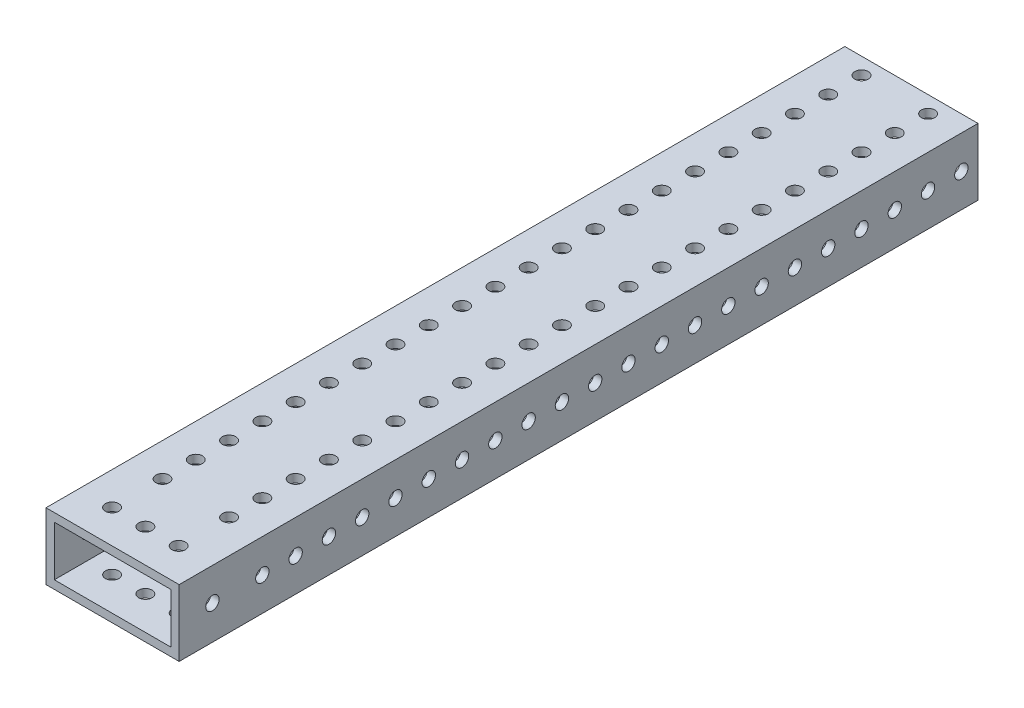
SolidWorks part; units mm, degrees
material "6061-T6 (SS)"
ref_plane "Front Plane" through (0, 0, 0) normal (0, 0, 1) x (1, 0, 0)
ref_plane "Top Plane" through (0, 0, 0) normal (0, 1, 0) x (1, 0, 0)
ref_plane "Right Plane" through (0, 0, 0) normal (1, 0, 0) x (0, 0, -1)
sketch "Sketch1" plane through (0, 0, 0) normal (0, 1, 0) x (1, 0, 0)
  line L1 (0, 0) -> (50.8, 0)
  line L2 (0, 0) -> (0, 304.8)
  line L3 (0, 304.8) -> (50.8, 304.8)
  line L4 (50.8, 0) -> (50.8, 304.8)
  dimension "D1" = 50.8
  dimension "D2" = 304.8
extrude "Boss-Extrude1" add sketch "Sketch1" along normal blind 25.4
sketch "Sketch2" plane through (0, 0, 0) normal (0, 0, 1) x (1, 0, 0)
  line L3 (3.175, 3.175) -> (47.625, 3.175)
  line L4 (3.175, 3.175) -> (3.175, 22.225)
  line L5 (3.175, 22.225) -> (47.625, 22.225)
  line L6 (47.625, 3.175) -> (47.625, 22.225)
  line L7 (0, 25.4) -> (0, 0) construction
  line L8 (50.8, 25.4) -> (50.8, 0) construction
  line L9 (0, 0) -> (50.8, 0) construction
  line L10 (0, 25.4) -> (50.8, 25.4) construction
  point P8 (25.4, 12.7)
  dimension "D1" = 3.175
  dimension "D2" = 3.175
  dimension "D3" = 3.175
  dimension "D4" = 3.175
extrude "Cut-Extrude1" cut sketch "Sketch2" against normal through all
sketch "Sketch4" plane through (0, 25.4, 0) normal (0, 1, 0) x (1, 0, 0)
  line L0 (0, 0) -> (50.8, 0) construction
  line L1 (0, 304.8) -> (0, 0) construction
  line L2 (50.8, 0) -> (50.8, 304.8) construction
  circle A0 centre (12.7, 6.35) radius 2.5527 construction
  circle A1 centre (38.1, 6.35) radius 2.5527 construction
  circle A2 centre (12.7, 19.05) radius 2.5527 construction
  circle A3 centre (38.1, 19.05) radius 2.5527 construction
  circle A4 centre (12.7, 31.75) radius 2.5527
  circle A5 centre (38.1, 31.75) radius 2.5527
  circle A6 centre (12.7, 44.45) radius 2.5527
  circle A7 centre (38.1, 44.45) radius 2.5527
  circle A8 centre (12.7, 57.15) radius 2.5527
  circle A9 centre (38.1, 57.15) radius 2.5527
  circle A10 centre (12.7, 69.85) radius 2.5527
  circle A11 centre (38.1, 69.85) radius 2.5527
  circle A12 centre (12.7, 82.55) radius 2.5527
  circle A13 centre (38.1, 82.55) radius 2.5527
  circle A14 centre (12.7, 95.25) radius 2.5527
  circle A15 centre (38.1, 95.25) radius 2.5527
  circle A16 centre (12.7, 107.95) radius 2.5527
  circle A17 centre (38.1, 107.95) radius 2.5527
  circle A18 centre (12.7, 120.65) radius 2.5527
  circle A19 centre (38.1, 120.65) radius 2.5527
  circle A20 centre (12.7, 133.35) radius 2.5527
  circle A21 centre (38.1, 133.35) radius 2.5527
  circle A22 centre (12.7, 146.05) radius 2.5527
  circle A23 centre (38.1, 146.05) radius 2.5527
  circle A24 centre (12.7, 158.75) radius 2.5527
  circle A25 centre (38.1, 158.75) radius 2.5527
  circle A26 centre (12.7, 171.45) radius 2.5527
  circle A27 centre (38.1, 171.45) radius 2.5527
  circle A28 centre (12.7, 184.15) radius 2.5527
  circle A29 centre (38.1, 184.15) radius 2.5527
  circle A30 centre (12.7, 196.85) radius 2.5527
  circle A31 centre (38.1, 196.85) radius 2.5527
  circle A32 centre (12.7, 209.55) radius 2.5527
  circle A33 centre (38.1, 209.55) radius 2.5527
  circle A34 centre (12.7, 222.25) radius 2.5527
  circle A35 centre (38.1, 222.25) radius 2.5527
  circle A36 centre (12.7, 234.95) radius 2.5527
  circle A37 centre (38.1, 234.95) radius 2.5527
  circle A38 centre (12.7, 247.65) radius 2.5527
  circle A39 centre (38.1, 247.65) radius 2.5527
  circle A40 centre (12.7, 260.35) radius 2.5527
  circle A41 centre (38.1, 260.35) radius 2.5527
  circle A42 centre (12.7, 273.05) radius 2.5527
  circle A43 centre (38.1, 273.05) radius 2.5527
  circle A44 centre (12.7, 285.75) radius 2.5527
  circle A45 centre (38.1, 285.75) radius 2.5527
  circle A46 centre (12.7, 298.45) radius 2.5527
  circle A47 centre (38.1, 298.45) radius 2.5527
  circle A48 centre (12.7, 311.15) radius 2.5527
  circle A49 centre (38.1, 311.15) radius 2.5527
  circle A50 centre (12.7, 323.85) radius 2.5527
  circle A51 centre (38.1, 323.85) radius 2.5527
  circle A52 centre (12.7, 336.55) radius 2.5527
  circle A53 centre (38.1, 336.55) radius 2.5527
  circle A54 centre (12.7, 349.25) radius 2.5527
  circle A55 centre (38.1, 349.25) radius 2.5527
  circle A56 centre (12.7, 361.95) radius 2.5527
  circle A57 centre (38.1, 361.95) radius 2.5527
  circle A58 centre (12.7, 374.65) radius 2.5527
  circle A59 centre (38.1, 374.65) radius 2.5527
  circle A60 centre (12.7, 387.35) radius 2.5527
  circle A61 centre (38.1, 387.35) radius 2.5527
  circle A62 centre (12.7, 400.05) radius 2.5527
  circle A63 centre (38.1, 400.05) radius 2.5527
  circle A64 centre (12.7, 412.75) radius 2.5527
  circle A65 centre (38.1, 412.75) radius 2.5527
  circle A66 centre (12.7, 425.45) radius 2.5527
  circle A67 centre (38.1, 425.45) radius 2.5527
  circle A68 centre (12.7, 438.15) radius 2.5527
  circle A69 centre (38.1, 438.15) radius 2.5527
  circle A70 centre (12.7, 450.85) radius 2.5527
  circle A71 centre (38.1, 450.85) radius 2.5527
  circle A72 centre (12.7, 463.55) radius 2.5527
  circle A73 centre (38.1, 463.55) radius 2.5527
  circle A74 centre (12.7, 476.25) radius 2.5527
  circle A75 centre (38.1, 476.25) radius 2.5527
  circle A76 centre (12.7, 488.95) radius 2.5527
  circle A77 centre (38.1, 488.95) radius 2.5527
  circle A78 centre (12.7, 501.65) radius 2.5527
  circle A79 centre (38.1, 501.65) radius 2.5527
  circle A81 centre (12.5095, 12.7) radius 2.5527
  circle A82 centre (25.2095, 12.7) radius 2.5527
  circle A84 centre (37.9095, 12.7) radius 2.5527
  dimension "D1" = 6.35
  dimension "D2" = 6.35
  dimension "D3" = 5.1054
  dimension "D4" = 5.1054
  dimension "D5" = 12.7
  dimension "D6" = 12.7
  dimension "D8" = 12.7
  dimension "D9" = 5.1054
  dimension "D10" = 12.5095
  dimension "D11" = 12.7
  dimension "D12" = 5.1054
  dimension "D13" = 12.7
  dimension "D14" = 12.7
  dimension "D15" = 12.7
  dimension "D16" = 5.1054
  dimension "D17" = 12.7
  dimension "D7" = 40
sketch "Sketch5" plane through (0, 0, 0) normal (-1, 0, 0) x (0, 0, 1)
  line L0 (-304.8, 0) -> (0, 0) construction
  line L1 (0, 25.4) -> (0, 0) construction
  line L3 (-116.3974, 0) -> (25.4, 0) construction
  line L4 (25.4, 76.2) -> (25.4, 0) construction
  circle A0 centre (-6.35, 12.7) radius 2.5527 construction
  circle A1 centre (-19.05, 12.7) radius 2.5527 construction
  circle A2 centre (-31.75, 12.7) radius 2.5527
  circle A3 centre (-44.45, 12.7) radius 2.5527
  circle A4 centre (-57.15, 12.7) radius 2.5527
  circle A5 centre (-69.85, 12.7) radius 2.5527
  circle A6 centre (-82.55, 12.7) radius 2.5527
  circle A7 centre (-95.25, 12.7) radius 2.5527
  circle A8 centre (-107.95, 12.7) radius 2.5527
  circle A9 centre (-120.65, 12.7) radius 2.5527
  circle A10 centre (-133.35, 12.7) radius 2.5527
  circle A11 centre (-146.05, 12.7) radius 2.5527
  circle A12 centre (-158.75, 12.7) radius 2.5527
  circle A13 centre (-171.45, 12.7) radius 2.5527
  circle A14 centre (-184.15, 12.7) radius 2.5527
  circle A15 centre (-196.85, 12.7) radius 2.5527
  circle A16 centre (-209.55, 12.7) radius 2.5527
  circle A17 centre (-222.25, 12.7) radius 2.5527
  circle A18 centre (-234.95, 12.7) radius 2.5527
  circle A19 centre (-247.65, 12.7) radius 2.5527
  circle A20 centre (-260.35, 12.7) radius 2.5527
  circle A21 centre (-273.05, 12.7) radius 2.5527
  circle A22 centre (-285.75, 12.7) radius 2.5527
  circle A23 centre (-298.45, 12.7) radius 2.5527
  circle A24 centre (-311.15, 12.7) radius 2.5527
  circle A25 centre (-323.85, 12.7) radius 2.5527
  circle A26 centre (-336.55, 12.7) radius 2.5527
  circle A27 centre (-349.25, 12.7) radius 2.5527
  circle A28 centre (-361.95, 12.7) radius 2.5527
  circle A29 centre (-374.65, 12.7) radius 2.5527
  circle A30 centre (-387.35, 12.7) radius 2.5527
  circle A31 centre (-400.05, 12.7) radius 2.5527
  circle A32 centre (-412.75, 12.7) radius 2.5527
  circle A33 centre (-425.45, 12.7) radius 2.5527
  circle A34 centre (-438.15, 12.7) radius 2.5527
  circle A35 centre (-450.85, 12.7) radius 2.5527
  circle A36 centre (-463.55, 12.7) radius 2.5527
  circle A37 centre (-476.25, 12.7) radius 2.5527
  circle A38 centre (-488.95, 12.7) radius 2.5527
  circle A39 centre (-501.65, 12.7) radius 2.5527
  circle A40 centre (-12.7, 12.954) radius 2.5527
  dimension "D1" = 12.7
  dimension "D2" = 6.35
  dimension "D3" = 5.1054
  dimension "D5" = 12.7
  dimension "D6" = 5.1054
  dimension "D7" = 12.954
  dimension "D8" = 38.1
  dimension "D4" = 40
extrude "Cut-Extrude2" cut sketch "Sketch4" against normal through all
extrude "Cut-Extrude3" cut sketch "Sketch5" against normal through all
